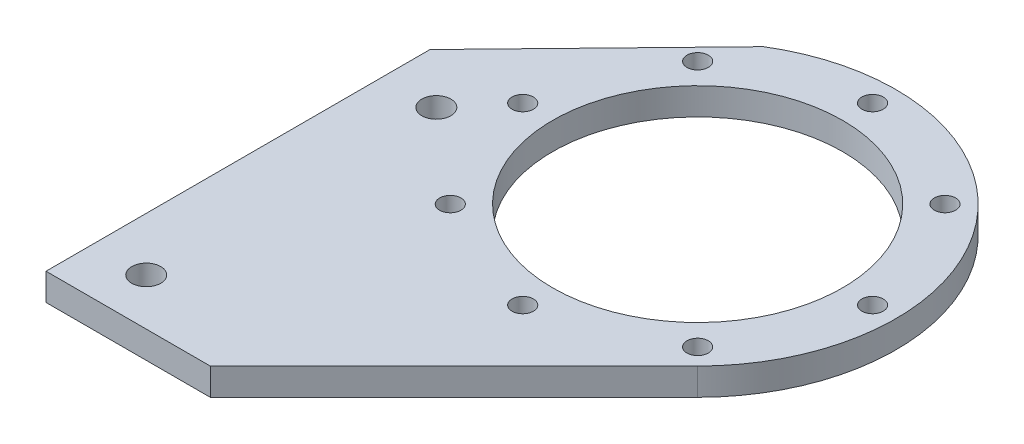
SolidWorks part; units mm, degrees
ref_plane "Front Plane" through (0, 0, 0) normal (0, 0, 1) x (1, 0, 0)
ref_plane "Top Plane" through (0, 0, 0) normal (0, 1, 0) x (1, 0, 0)
ref_plane "Right Plane" through (0, 0, 0) normal (1, 0, 0) x (0, 0, -1)
sketch "Sketch2" plane through (0, 0, 0) normal (0, 1, 0) x (1, 0, 0)
  line L0 (38.5109, 129.6827) -> (38.5109, 0) construction
  line L1 (0, 0) -> (38.5109, 0)
  line L2 (0, 0) -> (0, 90)
  line L6 (95.6305, 57.1195) -> (38.5109, 0)
  line L8 (0, 129.6827) -> (0, 90) construction
  line L9 (0, 90) -> (62.75, 90) construction
  line L10 (0, 90) -> (38.5109, 129.6827)
  arc A1 (38.5109, 129.6827) -> (95.6305, 57.1195) centre (62.75, 90) cw
  dimension "D1" = 90
  dimension "46.5" = 46.5
  dimension "D2" = 62.75
  dimension "D5" = 45
base flange "Base-Flange1" sketch "Sketch2" thickness 6.35 reverse thickness direction no parameters "D1"=0.7366
sketch "Sketch8" plane through (0, 0, 0) normal (0, 1, 0) x (1, 0, 0)
  line L1 (0, 90) -> (0, 0) construction
  line L2 (0, 45) -> (67.0707, 45) construction
  line L3 (0, 90) -> (109.25, 90) construction
  line L4 (67.0707, 28.5598) -> (67.0707, 90) construction
  line L5 (38.5109, 0) -> (95.6305, 57.1195) construction
  line L6 (0, 90) -> (0, 0) construction
  circle A1 centre (12.5, 79) radius 3.4
  circle A3 centre (12.5, 11) radius 3.4
  arc A4 (95.6305, 57.1195) -> (38.5109, 129.6827) centre (62.75, 90) ccw construction
  dimension "D1" = 6.8
  dimension "D3" = 12.5
  dimension "D2" = 11
extrude "Cut-Extrude1" cut sketch "Sketch8" against normal through all normal cut yes
sketch "Sketch9" plane through (0, 0, 0) normal (0, 1, 0) x (1, 0, 0)
  arc A0 (95.6305, 57.1195) -> (38.5109, 129.6827) centre (62.75, 90) ccw construction
  arc A1 (95.6305, 57.1195) -> (38.5109, 129.6827) centre (62.75, 90) ccw construction
  circle A2 centre (62.75, 90) radius 34
  dimension "D1" = 68
extrude "Cut-Extrude2" cut sketch "Sketch9" against normal through all normal cut yes
sketch "Sketch10" plane through (0, 0, 0) normal (0, 1, 0) x (1, 0, 0)
  circle A0 centre (62.75, 90) radius 41 construction
  circle A1 centre (62.75, 131) radius 2.5
  circle A2 centre (91.7414, 118.9914) radius 2.5
  circle A3 centre (103.75, 90) radius 2.5
  circle A4 centre (91.7414, 61.0086) radius 2.5
  circle A5 centre (62.75, 49) radius 2.5
  circle A6 centre (33.7586, 61.0086) radius 2.5
  circle A7 centre (21.75, 90) radius 2.5
  circle A8 centre (33.7586, 118.9914) radius 2.5
  point P22 (62.75, 90)
  dimension "D1" = 82
  dimension "D2" = 5
  dimension "D3" = 8
extrude "Cut-Extrude3" cut sketch "Sketch10" against normal through all normal cut yes
sketch "Bend-Lines1" [suppressed] plane through (0, 0, 0) normal (0, 1, 0) x (1, 0, 0)
sketch "Bounding-Box1" [suppressed] plane through (0, 0, 0) normal (0, 1, 0) x (1, 0, 0)
sheet metal parameters "Sheet-Metal1" thickness 6.35 parameters "D1"=0.7366
flat pattern "Flat-Pattern1" [suppressed]
sketch "Bend-Lines2" plane through (0, 0, 0) normal (0, 1, 0) x (1, 0, 0)
sketch3d "Bounding-Box2" [suppressed]
  line L0 (37.25, -37.25, 0) -> (37.25, 37.25, 0) construction
  line L1 (-22.5, -37.25, 0) -> (-22.5, 37.25, 0) construction
  line L2 (37.25, -37.25, 0) -> (-22.5, -37.25, 0) construction
  line L3 (37.25, 37.25, 0) -> (-22.5, 37.25, 0) construction
sheet metal parameters "Sheet-Metal2" thickness 6.35 parameters "D1"=0.7366
flat pattern "Flat-Pattern1"
sketch "Bend-Lines2" plane through (0, 0, 0) normal (0, 1, 0) x (1, 0, 0)
sketch3d "Bounding-Box2" [suppressed]
  line L0 (-106, -39.1795, 0) -> (-7.0705, 59.75, 0) construction
  line L1 (-46.25, -98.9295, 0) -> (52.6795, 0, 0) construction
  line L2 (-106, -39.1795, 0) -> (-46.25, -98.9295, 0) construction
  line L3 (-7.0705, 59.75, 0) -> (52.6795, 0, 0) construction
sheet metal parameters "Sheet-Metal3" thickness 6.35 parameters "D1"=0.7366
flat pattern "Flat-Pattern1"
sketch "Bend-Lines2" plane through (0, 0, 0) normal (0, 1, 0) x (1, 0, 0)
sketch3d "Bounding-Box2" [suppressed]
  line L0 (-107.7298, -46.3484, 0) -> (0.0689, 64.7304, 0) construction
  line L1 (-42.0452, -110.0934, 0) -> (65.7535, 0.9853, 0) construction
  line L2 (-107.7298, -46.3484, 0) -> (-42.0452, -110.0934, 0) construction
  line L3 (0.0689, 64.7304, 0) -> (65.7535, 0.9853, 0) construction
sheet metal parameters "Sheet-Metal4" thickness 6.35 parameters "D1"=0.7366
flat pattern "Flat-Pattern1"
sketch "Bend-Lines2" plane through (0, 0, 0) normal (0, 1, 0) x (1, 0, 0)
sketch3d "Bounding-Box2" [suppressed]
  line L0 (-107.7298, -46.3484, 0) -> (0.0689, 64.7304, 0) construction
  line L1 (-42.0452, -110.0934, 0) -> (65.7535, 0.9853, 0) construction
  line L2 (-107.7298, -46.3484, 0) -> (-42.0452, -110.0934, 0) construction
  line L3 (0.0689, 64.7304, 0) -> (65.7535, 0.9853, 0) construction
equation "\"L1L\"=500"
equation "\"L1Thick\"=6.35"
equation "\"Harm-Drive-Outer\"=74.5"
equation "\"L1-Spacing\"=115.65"
equation "\"L-Bracket-HoleToWall\"=12.5"
equation "\"Bracket-Hole-D\"=6.8"
equation "\"D1@Sketch8\"=\"Bracket-Hole-D\""
equation "\"L-Bracket-HoleToSide\"=11"
equation "\"D3@Sketch8\"=\"L-Bracket-HoleToWall\""
equation "\"D2@Sketch8\"=\"L-Bracket-HoleToSide\""
